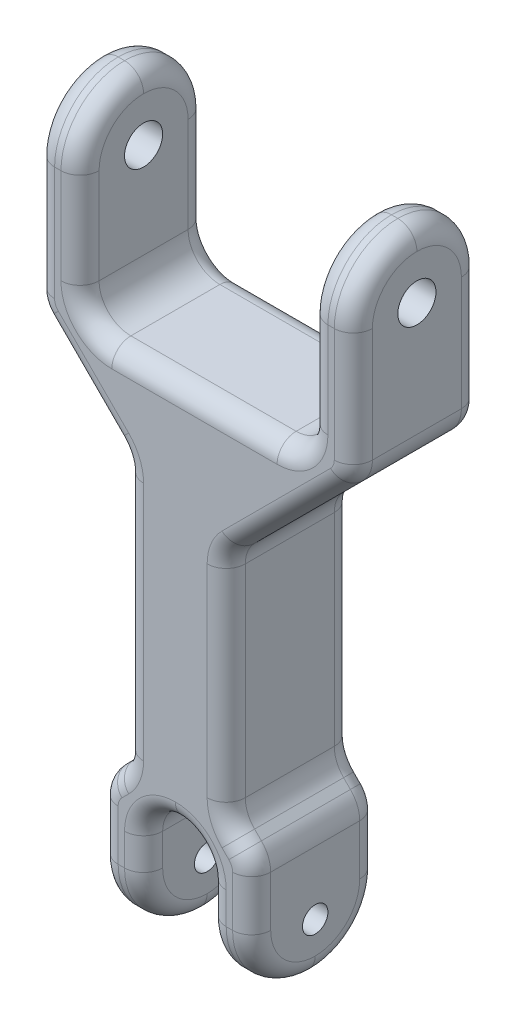
SolidWorks part; units mm, degrees
ref_plane "Front Plane" through (0, 0, 0) normal (0, 0, 1) x (1, 0, 0)
ref_plane "Top Plane" through (0, 0, 0) normal (0, 1, 0) x (1, 0, 0)
ref_plane "Right Plane" through (0, 0, 0) normal (1, 0, 0) x (0, 0, -1)
sketch "Sketch1" plane through (0, 0, 0) normal (0, 0, 1) x (1, 0, 0)
  line L0 (-15, 0) -> (-15, 20)
  line L1 (-15, 20) -> (-11, 24)
  line L2 (-11, 24) -> (-11, 66)
  line L3 (-11, 66) -> (-25, 80)
  line L4 (-25, 80) -> (-25, 110)
  line L5 (-25, 110) -> (25, 110)
  line L6 (25, 110) -> (25, 80)
  line L7 (25, 80) -> (5, 60)
  line L8 (5, 60) -> (5, 24)
  line L9 (5, 24) -> (9, 20)
  line L10 (9, 20) -> (9, 0)
  line L11 (9, 0) -> (-15, 0)
  line L13 (-18, 110) -> (18, 110)
  line L14 (-18, 110) -> (-18, 80)
  line L15 (-18, 80) -> (18, 80)
  line L16 (18, 110) -> (18, 80)
  line L17 (-8, 0) -> (2, 0)
  line L18 (-8, 0) -> (-8, 20)
  line L19 (-8, 20) -> (2, 20)
  line L20 (2, 0) -> (2, 20)
  dimension "D1" = 50
  dimension "D2" = 25
  dimension "D3" = 30
  dimension "D4" = 30
  dimension "D5" = 110
  dimension "D6" = 16
  dimension "D7" = 45
  dimension "D8" = 45
  dimension "D9" = 5
  dimension "D10" = 0
  dimension "D11" = 20
  dimension "D12" = 20
  dimension "D13" = 24
  dimension "D14" = 15
  dimension "D15" = 7
  dimension "D16" = 7
  dimension "D17" = 30
  dimension "D18" = 7
  dimension "D19" = 7
  dimension "D20" = 20
extrude "Boss-Extrude1" add sketch "Sketch1" along normal blind 10 and the other way blind 10 contours L20 L11 L10 L9 L8 L7 L6 L5 L16 L15 L14 L4 L3 L2 L1 L0 L18 L19 region at (-1.5046, 57.2901, 0)
sketch "Sketch2" plane through (25, 0, 0) normal (1, 0, 0) x (0, 0, -1)
  line L0 (10, 110) -> (-10, 110) construction
  line L1 (10, 110) -> (10, 80) construction
  line L2 (10, 0) -> (-10, 0) construction
  line L3 (10, 20) -> (10, 0) construction
  circle A0 centre (0, 100) radius 3
  circle A1 centre (0, 8) radius 2
  point P8 (0, 0)
  dimension "D1" = 10
  dimension "D2" = 6
  dimension "D3" = 10
  dimension "D4" = 4
  dimension "D5" = 8
  dimension "D6" = 10
extrude "Cut-Extrude1" cut sketch "Sketch2" against normal blind 50
fillet "Fillet4" radius 10 4 edges at (-21.5, 110, -10) (-21.5, 110, 10) (21.5, 110, -10) (21.5, 110, 10)
fillet "Fillet5" radius 5 2 edges at (18, 80, 0) (-18, 80, 0)
fillet "Fillet6" radius 5 8 edges at (-15, 20, 0) (-11, 24, 0) (-25, 80, 0) (-11, 66, 0) (9, 20, 0) (5, 24, 0) (5, 60, 0) (25, 80, 0)
fillet "Fillet9" radius 10 4 edges at (-11.5, 0, -10) (-11.5, 0, 10) (5.5, 0, -10) (5.5, 0, 10)
fillet "Fillet10" radius 5 2 edges at (-8, 20, 0) (2, 20, 0)
fillet "Fillet11" radius 3 70 edges at (18, 107.0711, 7.0711) (18, 107.0711, -7.0711) (18, 92.5, -10) (16.5355, 81.4645, -10) (0, 80, -10) (-16.5355, 81.4645, -10) (-18, 92.5, -10) (-18, 107.0711, -7.0711) (-18, 107.0711, 7.0711) (25, 107.0711, 7.0711) (25, 107.0711, -7.0711) (25, 91.0355, -10) (24.6194, 80.1577, -10) (15, 70, -10) (5.3806, 59.8423, -10) (5, 42, -10) (5.3806, 24.1577, -10) (7, 22, -10) (8.6194, 19.8423, -10) (9, 13.9645, -10) (9, 2.9289, -7.0711) (9, 2.9289, 7.0711) (-8, 2.9289, 7.0711) (-8, 2.9289, -7.0711) (-8, 12.5, -10) (-6.5355, 18.5355, -10) (0.5355, 18.5355, -10) (2, 12.5, -10) (2, 2.9289, -7.0711) (2, 2.9289, 7.0711) (-15, 2.9289, 7.0711) (-15, 2.9289, -7.0711) (-15, 13.9645, -10) (-14.6194, 19.8423, -10) (-13, 22, -10) (-11.3806, 24.1577, -10) (-11, 45, -10) (-11.3806, 65.8423, -10) (-18, 73, -10) (-24.6194, 80.1577, -10) (-25, 91.0355, -10) (-25, 107.0711, -7.0711) (-25, 107.0711, 7.0711) (-14.6194, 19.8423, 10) (-13, 22, 10) (-11.3806, 24.1577, 10) (-11, 45, 10) (-11.3806, 65.8423, 10) (-18, 73, 10) (-24.6194, 80.1577, 10) (-25, 91.0355, 10) (-18, 92.5, 10) (-16.5355, 81.4645, 10) (0, 80, 10) (16.5355, 81.4645, 10) (18, 92.5, 10) (25, 91.0355, 10) (24.6194, 80.1577, 10) (15, 70, 10) (5.3806, 59.8423, 10) (5, 42, 10) (5.3806, 24.1577, 10) (7, 22, 10) (8.6194, 19.8423, 10) (9, 13.9645, 10) (2, 12.5, 10) (0.5355, 18.5355, 10) (-6.5355, 18.5355, 10) (-8, 12.5, 10) (-15, 13.9645, 10)
